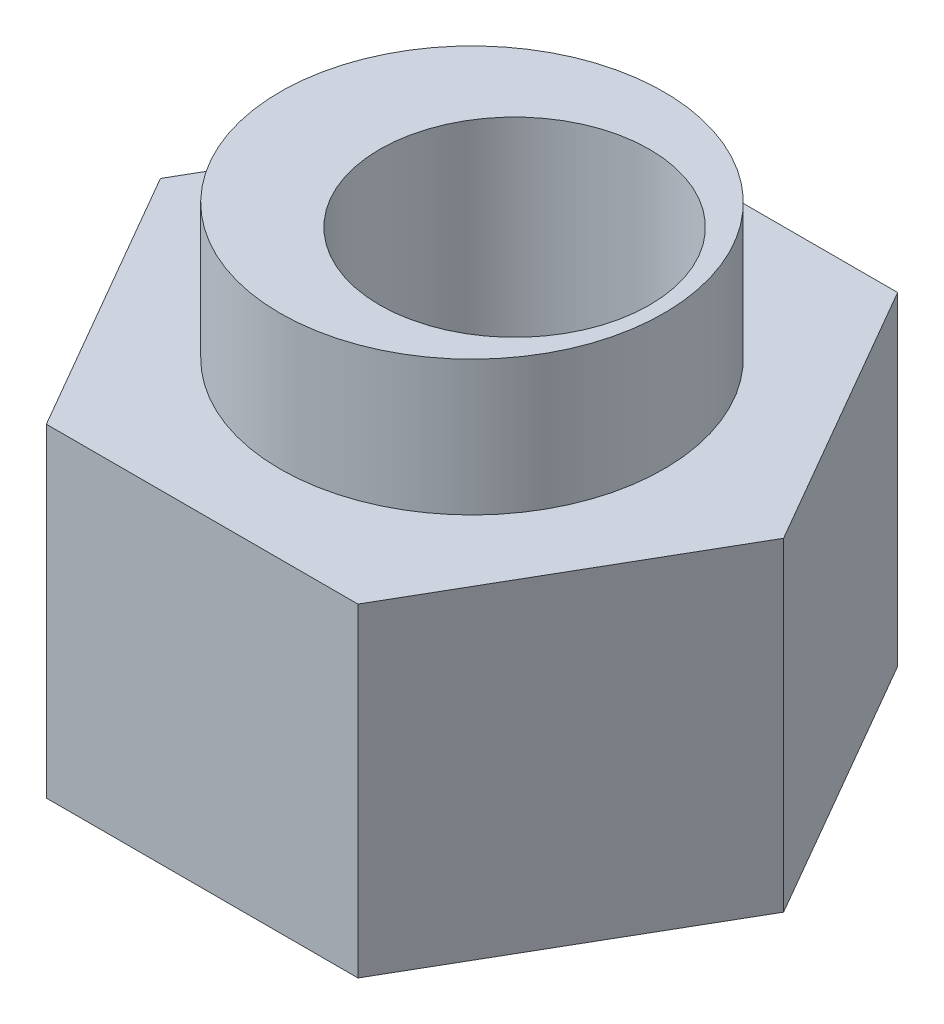
SolidWorks part; units mm, degrees
ref_plane "Спереди XY" through (0, 0, 0) normal (0, 0, 1) x (1, 0, 0)
ref_plane "Сверху XZ" through (0, 0, 0) normal (0, 1, 0) x (1, 0, 0)
ref_plane "Справа ZY" through (0, 0, 0) normal (1, 0, 0) x (0, 0, -1)
sketch "Эскиз1" plane through (0, 0, 0) normal (0, 1, 0) x (1, 0, 0)
  line L1 (-0.9282, 2.5575) -> (-6.7017, 2.5575)
  line L2 (-6.7017, 2.5575) -> (-9.5885, -2.4425)
  line L3 (-9.5885, -2.4425) -> (-6.7017, -7.4425)
  line L4 (-6.7017, -7.4425) -> (-0.9282, -7.4425)
  line L5 (-0.9282, -7.4425) -> (1.9585, -2.4425)
  line L6 (1.9585, -2.4425) -> (-0.9282, 2.5575)
  circle A0 centre (-3.815, -2.4425) radius 5 construction
  circle A1 centre (-3.815, -2.4425) radius 3.555
  circle A2 centre (-3.025, -2.4425) radius 2.5
  dimension "D2" = 7.11
  dimension "D3" = 5
  dimension "D1" = 10
  dimension "D4" = 0.79
extrude "Бобышка-Вытянуть1" add sketch "Эскиз1" against normal blind 6 contours L5 L6 L1 L2 L3 L4 A1 | A1 A2 region at (0.3829, 0, 0.0189) region at (-7.2694, 0, 2.4425)
extrude "Бобышка-Вытянуть2" add sketch "Эскиз1<3>" along normal blind 2.5 contours A1 A2 region at (-7.2694, 0, 2.4425)
sketch "Эскиз1<3>" plane through (0, 0, 0) normal (0, 1, 0) x (1, 0, 0) same geometry as "Эскиз1"
